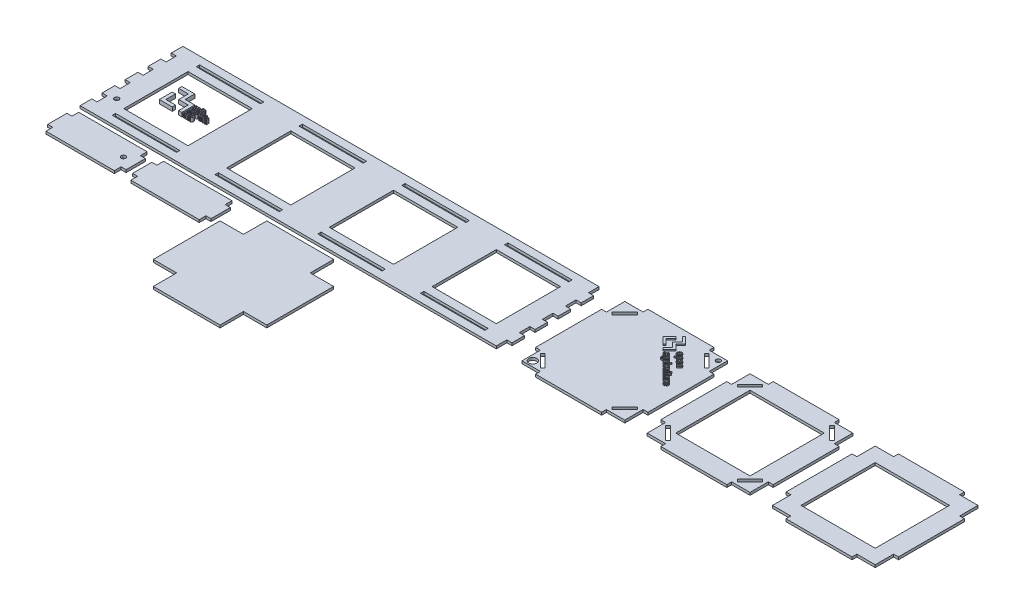
SolidWorks part; units mm, degrees
ref_plane "Front" through (0, 0, 0) normal (0, 0, 1) x (1, 0, 0)
ref_plane "Top" through (0, 0, 0) normal (0, 1, 0) x (1, 0, 0)
ref_plane "Right" through (0, 0, 0) normal (1, 0, 0) x (0, 0, -1)
sketch "Sketch1" plane through (0, 0, 0) normal (0, 1, 0) x (1, 0, 0)
  line L0 (0, 0) -> (152.4, 0) construction
  line L2 (-50.8, 50.8) -> (-50.8, -50.8) construction
  line L4 (50.8, 50.8) -> (50.8, -50.8) construction
  line L5 (-50.8, 50.8) -> (50.8, -50.8) construction
  line L6 (-50.8, -50.8) -> (50.8, 50.8) construction
  line L11 (50.8, 50.8) -> (152.4, 50.8)
  line L12 (50.8, 50.8) -> (50.8, -50.8) construction
  line L13 (50.8, -50.8) -> (152.4, -50.8)
  line L14 (152.4, 50.8) -> (152.4, -50.8) construction
  line L19 (-50.8, -50.8) -> (-152.4, -50.8)
  line L20 (-50.8, -50.8) -> (-50.8, 50.8) construction
  line L21 (-50.8, 50.8) -> (-152.4, 50.8)
  line L28 (50.8, -50.8) -> (-50.8, -50.8)
  line L34 (50.8, 50.8) -> (-50.8, 50.8)
  line L35 (-152.4, 50.8) -> (-152.4, -50.8) construction
  line L43 (-152.4, 50.8) -> (-254, 50.8)
  line L44 (-254, 50.8) -> (-254, -50.8) construction
  line L45 (-254, -50.8) -> (-152.4, -50.8)
  line L46 (152.4, 50.8) -> (152.4, 40.3352)
  line L47 (152.4, 40.3352) -> (157.48, 40.3352)
  line L48 (157.48, 40.3352) -> (157.48, 28.0162)
  line L49 (157.48, 28.0162) -> (152.4, 28.0162)
  line L50 (152.4, 28.0162) -> (152.4, 17.5514)
  line L51 (152.4, 17.5514) -> (157.48, 17.5514)
  line L63 (157.48, 17.5514) -> (157.48, 5.2324)
  line L64 (157.48, 5.2324) -> (152.4, 5.2324)
  line L65 (152.4, 5.2324) -> (152.4, -5.2324)
  line L66 (152.4, -5.2324) -> (157.48, -5.2324)
  line L67 (157.48, -5.2324) -> (157.48, -17.5514)
  line L68 (157.48, -17.5514) -> (152.4, -17.5514)
  line L69 (152.4, -17.5514) -> (152.4, -28.0162)
  line L70 (152.4, -28.0162) -> (157.48, -28.0162)
  line L71 (157.48, -28.0162) -> (157.48, -40.3352)
  line L72 (157.48, -40.3352) -> (152.4, -40.3352)
  line L73 (152.4, -40.3352) -> (152.4, -50.8)
  line L74 (-254, 50.8) -> (-259.08, 50.8)
  line L76 (-259.08, 39.2557) -> (-254, 39.2557)
  line L78 (-254, 29.0957) -> (-259.08, 29.0957)
  line L80 (-259.08, 16.4719) -> (-254, 16.4719)
  line L82 (-254, 6.3119) -> (-259.08, 6.3119)
  line L84 (-259.08, -6.3119) -> (-254, -6.3119)
  line L86 (-254, -16.4719) -> (-259.08, -16.4719)
  line L88 (-259.08, -29.0957) -> (-254, -29.0957)
  line L90 (-254, -39.2557) -> (-259.08, -39.2557)
  line L92 (-259.08, -50.8) -> (-254, -50.8)
  line L93 (157.48, 11.3919) -> (-254, 11.3919) construction
  line L94 (-254, 34.1757) -> (157.48, 34.1757) construction
  line L95 (-259.08, 50.8) -> (-259.08, 39.2557)
  line L96 (-259.08, 29.0957) -> (-259.08, 16.4719)
  line L97 (-254, 39.2557) -> (-254, 29.0957)
  line L98 (-254, 16.4719) -> (-254, 6.3119)
  line L99 (-254, -6.3119) -> (-254, -16.4719)
  line L100 (-254, -29.0957) -> (-254, -39.2557)
  line L101 (-254, -34.1757) -> (157.48, -34.1757) construction
  line L102 (-254, -11.3919) -> (157.48, -11.3919) construction
  line L103 (-259.08, 6.3119) -> (-259.08, -6.3119)
  line L104 (-259.08, -16.4719) -> (-259.08, -29.0957)
  line L105 (-259.08, -39.2557) -> (-259.08, -50.8)
  point P0 (0, 0)
  dimension "D1" = 101.6
  dimension "D2" = 101.6
  dimension "D3" = 5.08
  dimension "D4" = 12.319
  dimension "D5" = 10.16
extrude "Boss-Extrude1" add sketch "Sketch1" along normal blind 2.54
sketch "Sketch4" plane through (0, 2.54, 0) normal (0, 1, 0) x (1, 0, 0)
  line L0 (-152.4, 50.8) -> (-152.4, -50.8) construction
  line L1 (-152.4, 50.8) -> (-152.4, -50.8)
  line L2 (-50.8, 50.8) -> (-50.8, -50.8) construction
  line L3 (-50.8, 50.8) -> (-50.8, -50.8)
  line L4 (50.8, 50.8) -> (50.8, -50.8) construction
  line L5 (50.8, 50.8) -> (50.8, -50.8)
sketch "Sketch5" plane through (0, 2.54, 0) normal (0, 1, 0) x (1, 0, 0)
  line L0 (-254, -6.3119) -> (-254, 6.3119) construction
  line L1 (-152.4, 0) -> (-254, 0) construction
  line L2 (-152.4, 50.8) -> (-152.4, -50.8) construction
  line L3 (-152.4, 0) -> (-50.8, 0) construction
  line L4 (-50.8, 50.8) -> (-50.8, -50.8) construction
  line L5 (-50.8, 0) -> (50.8, 0) construction
  line L6 (50.8, 50.8) -> (50.8, -50.8) construction
  line L7 (50.8, 0) -> (152.4, 0) construction
  line L8 (152.4, -5.2324) -> (152.4, 5.2324) construction
  line L9 (-203.2, 0) -> (-203.2, -50.8) construction
  line L10 (-259.08, -50.8) -> (152.4, -50.8) construction
  line L11 (-101.6, 0) -> (-101.6, -50.8) construction
  line L12 (0, 0) -> (0, -50.8) construction
  line L13 (101.6, 0) -> (101.6, -50.8) construction
  line L14 (-171.45, -43.18) -> (-171.45, -50.8) construction
  line L15 (-234.95, -39.878) -> (-171.45, -39.878)
  line L16 (-234.95, -39.878) -> (-234.95, -43.18)
  line L17 (-234.95, -43.18) -> (-171.45, -43.18)
  line L18 (-171.45, -39.878) -> (-171.45, -43.18)
  line L19 (-234.95, -39.878) -> (-171.45, -43.18) construction
  line L20 (-234.95, -43.18) -> (-171.45, -39.878) construction
  line L21 (-133.35, -39.878) -> (-69.85, -39.878)
  line L22 (-133.35, -39.878) -> (-133.35, -43.18)
  line L23 (-133.35, -43.18) -> (-69.85, -43.18)
  line L24 (-69.85, -39.878) -> (-69.85, -43.18)
  line L25 (-133.35, -39.878) -> (-69.85, -43.18) construction
  line L26 (-133.35, -43.18) -> (-69.85, -39.878) construction
  line L27 (-31.75, -43.18) -> (31.75, -43.18)
  line L28 (-31.75, -43.18) -> (-31.75, -39.878)
  line L29 (-31.75, -39.878) -> (31.75, -39.878)
  line L30 (31.75, -43.18) -> (31.75, -39.878)
  line L31 (-31.75, -43.18) -> (31.75, -39.878) construction
  line L32 (-31.75, -39.878) -> (31.75, -43.18) construction
  line L33 (69.85, -43.18) -> (133.35, -43.18)
  line L34 (69.85, -43.18) -> (69.85, -39.878)
  line L35 (69.85, -39.878) -> (133.35, -39.878)
  line L36 (133.35, -43.18) -> (133.35, -39.878)
  line L37 (69.85, -43.18) -> (133.35, -39.878) construction
  line L38 (69.85, -39.878) -> (133.35, -43.18) construction
  line L39 (69.85, 39.878) -> (133.35, 43.18) construction
  line L40 (69.85, 43.18) -> (133.35, 39.878) construction
  line L41 (-31.75, 39.878) -> (31.75, 43.18) construction
  line L42 (-31.75, 43.18) -> (31.75, 39.878) construction
  line L43 (-133.35, 43.18) -> (-69.85, 39.878) construction
  line L44 (-133.35, 39.878) -> (-69.85, 43.18) construction
  line L45 (-234.95, 43.18) -> (-171.45, 39.878) construction
  line L46 (-234.95, 39.878) -> (-171.45, 43.18) construction
  line L47 (-171.45, 43.18) -> (-171.45, 50.8) construction
  line L48 (133.35, 43.18) -> (133.35, 39.878)
  line L49 (69.85, 39.878) -> (133.35, 39.878)
  line L50 (69.85, 43.18) -> (69.85, 39.878)
  line L51 (69.85, 43.18) -> (133.35, 43.18)
  line L52 (31.75, 43.18) -> (31.75, 39.878)
  line L53 (-31.75, 39.878) -> (31.75, 39.878)
  line L54 (-31.75, 43.18) -> (-31.75, 39.878)
  line L55 (-31.75, 43.18) -> (31.75, 43.18)
  line L56 (-69.85, 39.878) -> (-69.85, 43.18)
  line L57 (-133.35, 43.18) -> (-69.85, 43.18)
  line L58 (-133.35, 39.878) -> (-133.35, 43.18)
  line L59 (-133.35, 39.878) -> (-69.85, 39.878)
  line L60 (-171.45, 39.878) -> (-171.45, 43.18)
  line L61 (-234.95, 43.18) -> (-171.45, 43.18)
  line L62 (-234.95, 39.878) -> (-234.95, 43.18)
  line L63 (-234.95, 39.878) -> (-171.45, 39.878)
  line L65 (-234.95, 31.75) -> (-171.45, 31.75)
  line L66 (-234.95, 31.75) -> (-234.95, -31.75)
  line L67 (-234.95, -31.75) -> (-171.45, -31.75)
  line L68 (-171.45, 31.75) -> (-171.45, -31.75)
  line L69 (-234.95, 31.75) -> (-171.45, -31.75) construction
  line L70 (-234.95, -31.75) -> (-171.45, 31.75) construction
  line L71 (-133.35, 31.75) -> (-69.85, 31.75)
  line L72 (-133.35, 31.75) -> (-133.35, -31.75)
  line L73 (-133.35, -31.75) -> (-69.85, -31.75)
  line L74 (-69.85, 31.75) -> (-69.85, -31.75)
  line L75 (-133.35, 31.75) -> (-69.85, -31.75) construction
  line L76 (-133.35, -31.75) -> (-69.85, 31.75) construction
  line L77 (-31.75, 31.75) -> (31.75, 31.75)
  line L78 (-31.75, 31.75) -> (-31.75, -31.75)
  line L79 (-31.75, -31.75) -> (31.75, -31.75)
  line L80 (31.75, 31.75) -> (31.75, -31.75)
  line L81 (-31.75, 31.75) -> (31.75, -31.75) construction
  line L82 (-31.75, -31.75) -> (31.75, 31.75) construction
  line L83 (69.85, 31.75) -> (133.35, 31.75)
  line L84 (69.85, 31.75) -> (69.85, -31.75)
  line L85 (69.85, -31.75) -> (133.35, -31.75)
  line L86 (133.35, 31.75) -> (133.35, -31.75)
  line L87 (69.85, 31.75) -> (133.35, -31.75) construction
  line L88 (69.85, -31.75) -> (133.35, 31.75) construction
  circle A0 centre (-246.95, -26.75) radius 2.2225
  point P27 (-203.2, -41.529)
  point P32 (-101.6, -41.529)
  point P37 (0, -41.529)
  point P42 (101.6, -41.529)
  point P66 (101.6, 41.529)
  point P67 (0, 41.529)
  point P68 (-101.6, 41.529)
  point P69 (-203.2, 41.529)
  dimension "D5" = 4.445
  dimension "D7" = 5
  dimension "D1" = 7.62
  dimension "D2" = 3.302
  dimension "D3" = 63.5
  dimension "D4" = 63.5
  dimension "D6" = 12
extrude "Cut-Extrude2" cut sketch "Sketch5" against normal through all
sketch "Sketch6" plane through (0, 0, 0) normal (0, 1, 0) x (1, 0, 0)
  line L0 (0, 0) -> (228.6, 0) construction
  line L1 (228.6, 0) -> (228.6, 53.1812) construction
  line L2 (177.8, 50.8) -> (279.4, 50.8) construction
  line L3 (177.8, 50.8) -> (177.8, -50.8) construction
  line L4 (177.8, -50.8) -> (279.4, -50.8) construction
  line L5 (279.4, 50.8) -> (279.4, -50.8) construction
  line L6 (177.8, 50.8) -> (279.4, -50.8) construction
  line L7 (177.8, -50.8) -> (279.4, 50.8) construction
  line L8 (228.6, 0) -> (281.7812, 0) construction
  line L9 (228.6, 0) -> (228.6, -53.1812) construction
  line L10 (177.8, 32.639) -> (177.8, 50.8)
  line L11 (195.961, 55.5625) -> (261.239, 55.5625)
  line L12 (195.961, 55.5625) -> (195.961, 50.8)
  line L13 (195.961, 50.8) -> (261.239, 50.8) construction
  line L14 (261.239, 55.5625) -> (261.239, 50.8)
  line L15 (195.961, 55.5625) -> (261.239, 50.8) construction
  line L16 (195.961, 50.8) -> (261.239, 55.5625) construction
  line L17 (284.1625, -32.639) -> (279.4, -32.639)
  line L18 (284.1625, -32.639) -> (284.1625, 32.639)
  line L19 (284.1625, 32.639) -> (279.4, 32.639)
  line L20 (279.4, -32.639) -> (279.4, 32.639) construction
  line L21 (284.1625, -32.639) -> (279.4, 32.639) construction
  line L22 (284.1625, 32.639) -> (279.4, -32.639) construction
  line L23 (195.961, -55.5625) -> (261.239, -55.5625)
  line L24 (195.961, -55.5625) -> (195.961, -50.8)
  line L25 (195.961, -50.8) -> (261.239, -50.8) construction
  line L26 (261.239, -55.5625) -> (261.239, -50.8)
  line L27 (195.961, -55.5625) -> (261.239, -50.8) construction
  line L28 (195.961, -50.8) -> (261.239, -55.5625) construction
  line L29 (173.0375, 32.639) -> (177.8, 32.639)
  line L30 (173.0375, 32.639) -> (173.0375, -32.639)
  line L31 (173.0375, -32.639) -> (177.8, -32.639)
  line L32 (177.8, 32.639) -> (177.8, -32.639) construction
  line L33 (173.0375, 32.639) -> (177.8, -32.639) construction
  line L34 (173.0375, -32.639) -> (177.8, 32.639) construction
  line L35 (177.8, 50.8) -> (195.961, 50.8)
  line L36 (261.239, 50.8) -> (279.4, 50.8)
  line L37 (279.4, 50.8) -> (279.4, 32.639)
  line L38 (279.4, -32.639) -> (279.4, -50.8)
  line L39 (279.4, -50.8) -> (261.239, -50.8)
  line L40 (195.961, -50.8) -> (177.8, -50.8)
  line L41 (177.8, -50.8) -> (177.8, -32.639)
  line L42 (296.8625, 32.639) -> (296.8625, -32.639)
  line L43 (296.8625, 32.639) -> (301.625, 32.639)
  line L44 (301.625, 32.639) -> (301.625, 50.8)
  line L45 (301.625, 50.8) -> (319.786, 50.8)
  line L46 (319.786, 55.5625) -> (319.786, 50.8)
  line L47 (319.786, 55.5625) -> (385.064, 55.5625)
  line L48 (385.064, 55.5625) -> (385.064, 50.8)
  line L49 (385.064, 50.8) -> (403.225, 50.8)
  line L50 (403.225, 50.8) -> (403.225, 32.639)
  line L51 (407.9875, 32.639) -> (403.225, 32.639)
  line L52 (407.9875, -32.639) -> (407.9875, 32.639)
  line L53 (407.9875, -32.639) -> (403.225, -32.639)
  line L54 (403.225, -32.639) -> (403.225, -50.8)
  line L55 (403.225, -50.8) -> (385.064, -50.8)
  line L56 (385.064, -55.5625) -> (385.064, -50.8)
  line L57 (319.786, -55.5625) -> (385.064, -55.5625)
  line L58 (319.786, -55.5625) -> (319.786, -50.8)
  line L59 (319.786, -50.8) -> (301.625, -50.8)
  line L60 (301.625, -50.8) -> (301.625, -32.639)
  line L61 (296.8625, -32.639) -> (301.625, -32.639)
  line L62 (301.625, 50.8) -> (403.225, -50.8) construction
  line L63 (420.6875, 32.639) -> (420.6875, -32.639)
  line L64 (420.6875, 32.639) -> (425.45, 32.639)
  line L65 (425.45, 32.639) -> (425.45, 50.8)
  line L66 (425.45, 50.8) -> (443.611, 50.8)
  line L67 (443.611, 55.5625) -> (443.611, 50.8)
  line L68 (443.611, 55.5625) -> (508.889, 55.5625)
  line L69 (508.889, 55.5625) -> (508.889, 50.8)
  line L70 (508.889, 50.8) -> (527.05, 50.8)
  line L71 (527.05, 50.8) -> (527.05, 32.639)
  line L72 (531.8125, 32.639) -> (527.05, 32.639)
  line L73 (531.8125, -32.639) -> (531.8125, 32.639)
  line L74 (531.8125, -32.639) -> (527.05, -32.639)
  line L75 (527.05, -32.639) -> (527.05, -50.8)
  line L76 (527.05, -50.8) -> (508.889, -50.8)
  line L77 (508.889, -55.5625) -> (508.889, -50.8)
  line L78 (443.611, -55.5625) -> (508.889, -55.5625)
  line L79 (443.611, -55.5625) -> (443.611, -50.8)
  line L80 (443.611, -50.8) -> (425.45, -50.8)
  line L81 (425.45, -50.8) -> (425.45, -32.639)
  line L82 (420.6875, -32.639) -> (425.45, -32.639)
  line L83 (425.45, 50.8) -> (527.05, -50.8) construction
  line L84 (315.722, 36.703) -> (389.128, 36.703)
  line L85 (315.722, 36.703) -> (315.722, -36.703)
  line L86 (315.722, -36.703) -> (389.128, -36.703)
  line L87 (389.128, 36.703) -> (389.128, -36.703)
  line L88 (315.722, 36.703) -> (389.128, -36.703) construction
  line L89 (315.722, -36.703) -> (389.128, 36.703) construction
  line L91 (512.953, 36.703) -> (439.547, 36.703)
  line L92 (512.953, 36.703) -> (512.953, -36.703)
  line L93 (512.953, -36.703) -> (439.547, -36.703)
  line L94 (439.547, 36.703) -> (439.547, -36.703)
  line L95 (512.953, 36.703) -> (439.547, -36.703) construction
  line L96 (512.953, -36.703) -> (439.547, 36.703) construction
  point P22 (175.4187, 0)
  point P67 (352.425, 0)
  point P72 (476.25, 0)
  dimension "D1" = 101.6
  dimension "D2" = 101.6
  dimension "D3" = 4.7625
  dimension "D4" = 65.278
  dimension "D5" = 228.6
  dimension "D7" = 12.7
  dimension "D8" = 73.406
  dimension "D6" = 3
extrude "Boss-Extrude2" add sketch "Sketch6" along normal blind 2.54 separate body
sketch "Sketch7" plane through (0, 0, 0) normal (0, 1, 0) x (1, 0, 0)
  line L0 (-234.95, 39.878) -> (-234.95, -27.686) construction
  line L1 (-254.08, -57.15) -> (-186.516, -57.15)
  line L2 (-254.08, -57.15) -> (-254.08, -63.8175)
  line L3 (-254.08, -89.535) -> (-186.516, -89.535)
  line L4 (-186.516, -57.15) -> (-186.516, -63.8175)
  line L5 (-254.08, -57.15) -> (-186.516, -89.535) construction
  line L6 (-254.08, -89.535) -> (-186.516, -57.15) construction
  line L7 (-234.95, 31.75) -> (-234.95, -31.75) construction
  line L8 (-234.95, -27.686) -> (-234.95, -31.75) construction
  line L9 (177.8, -32.639) -> (177.8, -50.8) construction
  line L10 (177.8, -50.8) -> (195.961, -50.8) construction
  line L12 (-254.08, -63.8175) -> (-259.08, -63.8175)
  line L13 (182.9292, -33.0985) -> (195.5015, -45.6708) construction
  line L14 (182.9292, -33.0985) -> (180.5943, -35.4333) construction
  line L15 (180.5943, -35.4333) -> (193.1667, -48.0057) construction
  line L16 (195.5015, -45.6708) -> (193.1667, -48.0057) construction
  line L17 (182.9292, -33.0985) -> (193.1667, -48.0057) construction
  line L18 (180.5943, -35.4333) -> (195.5015, -45.6708) construction
  line L19 (-259.08, -63.8175) -> (-259.08, -82.8675)
  line L20 (-259.08, -82.8675) -> (-254.08, -82.8675)
  line L21 (177.8, -32.639) -> (195.961, -50.8) construction
  line L22 (188.0479, -40.5521) -> (186.8805, -41.7195) construction
  line L23 (-254.08, -82.8675) -> (-254.08, -89.535)
  line L24 (-186.516, -63.8175) -> (-181.516, -63.8175)
  line L25 (-181.516, -63.8175) -> (-181.516, -82.8675)
  line L26 (-181.516, -82.8675) -> (-186.516, -82.8675)
  line L27 (-186.516, -82.8675) -> (-186.516, -89.535)
  line L28 (-259.08, -50.8) -> (152.4, -50.8) construction
  line L29 (-259.08, -39.2557) -> (-259.08, -50.8) construction
  line L30 (-170.166, -57.15) -> (-102.602, -57.15)
  line L31 (-170.166, -57.15) -> (-170.166, -63.8175)
  line L32 (-170.166, -89.535) -> (-102.602, -89.535)
  line L33 (-102.602, -57.15) -> (-102.602, -63.8175)
  line L34 (-170.166, -63.8175) -> (-175.166, -63.8175)
  line L35 (-175.166, -63.8175) -> (-175.166, -82.8675)
  line L36 (-175.166, -82.8675) -> (-170.166, -82.8675)
  line L37 (-170.166, -82.8675) -> (-170.166, -89.535)
  line L38 (-102.602, -63.8175) -> (-97.602, -63.8175)
  line L39 (-97.602, -63.8175) -> (-97.602, -82.8675)
  line L40 (-97.602, -82.8675) -> (-102.602, -82.8675)
  line L41 (-102.602, -82.8675) -> (-102.602, -89.535)
  line L42 (-170.166, -57.15) -> (-102.602, -89.535) construction
  line L43 (-170.166, -89.535) -> (-102.602, -57.15) construction
  point P0 (-220.298, -73.3425)
  point P14 (188.0479, -40.5521)
  point P38 (-136.384, -73.3425)
  dimension "D1" = 32.385
  dimension "D2" = 4.064
  dimension "D3" = 3.302
  dimension "D4" = 19.05
  dimension "D5" = 17.78
  dimension "D6" = 5
  dimension "D7" = 6.35
  dimension "D9" = 6.35
  dimension "D8" = 2
extrude "Boss-Extrude3" add sketch "Sketch7" along normal blind 2.54 separate body
sketch "Sketch8" plane through (0, 2.54, 0) normal (0, 1, 0) x (1, 0, 0)
  line L0 (180.5943, -35.4333) -> (193.1667, -48.0057) construction
  line L1 (195.5015, -45.6708) -> (193.1667, -48.0057) construction
  line L2 (182.9292, -33.0985) -> (195.5015, -45.6708) construction
  line L3 (182.9292, -33.0985) -> (180.5943, -35.4333) construction
  line L4 (180.5943, -35.4333) -> (193.1667, -48.0057)
  line L5 (195.5015, -45.6708) -> (193.1667, -48.0057)
  line L6 (182.9292, -33.0985) -> (195.5015, -45.6708)
  line L7 (182.9292, -33.0985) -> (180.5943, -35.4333)
  line L8 (177.8, 50.8) -> (279.4, -50.8) construction
  line L9 (195.5015, 45.6708) -> (182.9292, 33.0985)
  line L10 (195.5015, 45.6708) -> (193.1667, 48.0057)
  line L11 (193.1667, 48.0057) -> (180.5943, 35.4333)
  line L12 (182.9292, 33.0985) -> (180.5943, 35.4333)
  line L13 (274.2708, 33.0985) -> (261.6985, 45.6708)
  line L14 (274.2708, 33.0985) -> (276.6057, 35.4333)
  line L15 (276.6057, 35.4333) -> (264.0333, 48.0057)
  line L16 (261.6985, 45.6708) -> (264.0333, 48.0057)
  line L17 (261.6985, -45.6708) -> (274.2708, -33.0985)
  line L18 (261.6985, -45.6708) -> (264.0333, -48.0057)
  line L19 (264.0333, -48.0057) -> (276.6057, -35.4333)
  line L20 (274.2708, -33.0985) -> (276.6057, -35.4333)
  line L21 (301.625, -32.639) -> (319.786, -50.8) construction
  line L22 (304.4193, -35.4333) -> (306.7542, -33.0985)
  line L23 (306.7542, -33.0985) -> (319.3265, -45.6708)
  line L24 (319.3265, -45.6708) -> (316.9917, -48.0057)
  line L25 (310.7055, -41.7195) -> (313.0404, -39.3846) construction
  line L26 (304.4193, -35.4333) -> (316.9917, -48.0057)
  line L27 (301.625, 50.8) -> (403.225, -50.8) construction
  line L28 (306.7542, 33.0985) -> (304.4193, 35.4333)
  line L29 (316.9917, 48.0057) -> (304.4193, 35.4333)
  line L30 (316.9917, 48.0057) -> (319.3265, 45.6708)
  line L31 (319.3265, 45.6708) -> (306.7542, 33.0985)
  line L32 (385.5235, 45.6708) -> (387.8583, 48.0057)
  line L33 (400.4307, 35.4333) -> (387.8583, 48.0057)
  line L34 (400.4307, 35.4333) -> (398.0958, 33.0985)
  line L35 (398.0958, 33.0985) -> (385.5235, 45.6708)
  line L36 (398.0958, -33.0985) -> (400.4307, -35.4333)
  line L37 (387.8583, -48.0057) -> (400.4307, -35.4333)
  line L38 (387.8583, -48.0057) -> (385.5235, -45.6708)
  line L39 (385.5235, -45.6708) -> (398.0958, -33.0985)
  circle A0 centre (228.6, 0) radius 20.7898 construction
  circle A1 centre (228.6, 0) radius 20.7898 construction
  circle A2 centre (228.6, 0) radius 20.7898 construction
  circle A3 centre (228.6, 0) radius 20.7898 construction
  circle A4 centre (352.425, 0) radius 51.9059 construction
  point P28 (228.6, 0)
  point P58 (352.425, 0)
  dimension "D1" = 4
  dimension "D2" = 4
extrude "Cut-Extrude3" cut sketch "Sketch8" against normal through all
sketch "Sketch10" plane through (0, 2.54, 0) normal (0, 1, 0) x (1, 0, 0)
  line L0 (-171.45, 31.75) -> (-234.95, 31.75) construction
  line L1 (-69.85, 31.75) -> (-133.35, 31.75) construction
  line L2 (31.75, 31.75) -> (-31.75, 31.75) construction
  line L3 (133.35, 31.75) -> (69.85, 31.75) construction
  line L4 (-196.85, 31.75) -> (-209.55, 31.75)
  line L5 (-95.25, 31.75) -> (-107.95, 31.75)
  line L6 (6.35, 31.75) -> (-6.35, 31.75)
  line L7 (107.95, 31.75) -> (95.25, 31.75)
  line L8 (-234.95, -27.686) -> (-171.45, -27.686)
  line L9 (-203.2, -27.686) -> (-203.2, -31.75) construction
  line L14 (-234.95, 31.75) -> (-234.95, -31.75) construction
  line L15 (-171.45, -31.75) -> (-171.45, 31.75) construction
  line L16 (-234.95, -31.75) -> (-171.45, -31.75) construction
  line L17 (-133.35, -27.686) -> (-69.85, -27.686)
  line L18 (-133.35, 31.75) -> (-133.35, -31.75) construction
  line L19 (-69.85, -31.75) -> (-69.85, 31.75) construction
  line L20 (-31.75, -27.686) -> (31.75, -27.686)
  line L21 (-31.75, 31.75) -> (-31.75, -31.75) construction
  line L22 (31.75, -31.75) -> (31.75, 31.75) construction
  line L23 (69.85, -27.686) -> (133.35, -27.686)
  line L24 (69.85, 31.75) -> (69.85, -31.75) construction
  line L25 (133.35, -31.75) -> (133.35, 31.75) construction
  line L27 (-234.95, 31.75) -> (-234.95, -27.686) construction
  arc A0 (-209.55, 31.75) -> (-196.85, 31.75) centre (-203.2, 31.75) ccw
  arc A1 (-107.95, 31.75) -> (-95.25, 31.75) centre (-101.6, 31.75) ccw
  arc A2 (-6.35, 31.75) -> (6.35, 31.75) centre (0, 31.75) ccw
  arc A3 (95.25, 31.75) -> (107.95, 31.75) centre (101.6, 31.75) ccw
  dimension "D1" = 12.7
  dimension "D2" = 4.064
sketch "Sketch11" plane through (0, 0, 0) normal (0, 1, 0) x (1, 0, 0)
  line L0 (-133.35, -31.75) -> (-133.35, -39.878) construction
  line L5 (-68.138, -80.264) -> (-2.098, -80.264) construction
  line L6 (-68.138, -80.264) -> (-68.138, -146.304) construction
  line L7 (-68.138, -146.304) -> (-2.098, -146.304) construction
  line L8 (-2.098, -80.264) -> (-2.098, -146.304) construction
  line L9 (-68.138, -80.264) -> (-2.098, -146.304) construction
  line L10 (-68.138, -146.304) -> (-2.098, -80.264) construction
  line L11 (-68.138, -80.264) -> (-91.252, -80.264)
  line L12 (-91.252, -80.264) -> (-91.252, -146.304)
  line L13 (-91.252, -146.304) -> (-68.138, -146.304)
  line L14 (-68.138, -80.264) -> (-68.138, -57.15)
  line L15 (-68.138, -57.15) -> (-2.098, -57.15)
  line L16 (-2.098, -57.15) -> (-2.098, -80.264)
  line L17 (-2.098, -80.264) -> (21.016, -80.264)
  line L18 (21.016, -80.264) -> (21.016, -146.304)
  line L19 (21.016, -146.304) -> (-2.098, -146.304)
  line L20 (-2.098, -146.304) -> (-2.098, -169.418)
  line L21 (-2.098, -169.418) -> (-68.138, -169.418)
  line L22 (-68.138, -169.418) -> (-68.138, -146.304)
  line L23 (-259.08, -50.8) -> (152.4, -50.8) construction
  line L24 (-97.602, -82.8675) -> (-97.602, -63.8175) construction
  line L27 (133.35, -27.686) -> (133.35, -50.8) construction
  point P0 (-35.118, -113.284)
  dimension "D1" = 66.04
  dimension "D4" = 6.35
  dimension "D5" = 6.35
extrude "Boss-Extrude5" add sketch "Sketch11" along normal blind 2.54 separate body
sketch "Sketch12" plane through (0, 2.54, 0) normal (0, 1, 0) x (1, 0, 0)
  line L0 (-68.138, -80.264) -> (-2.098, -80.264)
  line L1 (-2.098, -80.264) -> (-2.098, -146.304)
  line L2 (-2.098, -146.304) -> (-68.138, -146.304)
  line L3 (-68.138, -80.264) -> (-68.138, -146.304)
sketch "Sketch13" plane through (0, 0, 0) normal (0, 1, 0) x (1, 0, 0)
  line L16 (-223.9443, 14.6616) -> (-211.1797, 14.6616)
  line L17 (-211.1797, 14.6616) -> (-211.1797, 5.1786)
  line L18 (-211.1797, 5.1786) -> (-201.7193, 5.1786)
  line L19 (239.1402, 49.5353) -> (245.5874, 43.0882)
  line L20 (245.5874, 43.0882) -> (240.7977, 38.2986)
  line L21 (240.7977, 38.2986) -> (245.5759, 33.5204)
  line L22 (245.5759, 33.5204) -> (239.1174, 27.0618)
  line L24 (237.5056, 28.6736) -> (242.3295, 33.4975)
  line L25 (242.3295, 33.4975) -> (237.5627, 38.2643)
  line L26 (237.5627, 38.2643) -> (242.3752, 43.0768)
  line L27 (242.3752, 43.0768) -> (237.5284, 47.9235)
  line L28 (237.5284, 47.9235) -> (239.1402, 49.5353)
  line L29 (234.3506, 44.7457) -> (235.9738, 43.1225)
  line L30 (235.9738, 43.1225) -> (231.1385, 38.2871)
  line L31 (231.1385, 38.2871) -> (235.9624, 33.4632)
  line L32 (235.9624, 33.4632) -> (234.3392, 31.84)
  line L33 (234.3392, 31.84) -> (227.892, 38.2871)
  line L34 (227.892, 38.2871) -> (234.3506, 44.7457)
  line L36 (239.5771, 26.9975) -> (266.5291, 0.0455) construction
  line L37 (247.4273, 32.1428) -> (285.1667, -5.5965) construction
  line L38 (237.5056, 28.6736) -> (239.1174, 27.0618)
  line L41 (-201.7193, 5.1786) -> (-201.7193, -7.6086)
  line L43 (-204.9105, -7.6086) -> (-204.9105, 1.9422)
  line L44 (-204.9105, 1.9422) -> (-214.3482, 1.9422)
  line L45 (-214.3482, 1.9422) -> (-214.3482, 11.4705)
  line L46 (-214.3482, 11.4705) -> (-223.9443, 11.4705)
  line L47 (-223.9443, 11.4705) -> (-223.9443, 14.6616)
  line L48 (-223.9443, 5.1786) -> (-220.7305, 5.1786)
  line L49 (-220.7305, 5.1786) -> (-220.7305, -4.3949)
  line L50 (-220.7305, -4.3949) -> (-211.1797, -4.3949)
  line L51 (-211.1797, -4.3949) -> (-211.1797, -7.6086)
  line L52 (-211.1797, -7.6086) -> (-223.9443, -7.6086)
  line L53 (-223.9443, -7.6086) -> (-223.9443, 5.1786)
  line L54 (-200.854, -7.608) -> (-149.188, -7.608) construction
  line L55 (-234.95, 31.75) -> (-171.45, -27.686) construction
  line L56 (-204.9105, -7.6086) -> (-201.7193, -7.6086)
  line L57 (-200.854, -7.608) -> (-200.854, 5.1786) construction
  line L58 (-200.854, 5.1786) -> (-201.7193, 5.1786) construction
  line L59 (-200.854, 1.9422) -> (-182.9615, 1.9422) construction
  line L60 (-200.854, -2.3557) -> (-181.4784, -2.3557) construction
  line L61 (-234.95, 31.75) -> (-234.95, -31.75) construction
  line L62 (-196.85, 6.35) -> (-209.55, 6.35) construction
  line L63 (-196.85, 6.35) -> (-196.85, -2.286) construction
  line L64 (-196.85, -2.286) -> (-209.55, -2.286) construction
  line L65 (-209.55, 6.35) -> (-209.55, -2.286) construction
  line L66 (-196.85, 6.35) -> (-209.55, -2.286) construction
  line L67 (-196.85, -2.286) -> (-209.55, 6.35) construction
  line L68 (-171.45, 31.75) -> (-234.95, 31.75) construction
  line L69 (-234.95, -27.686) -> (-171.45, -27.686) construction
  line L70 (-171.45, -31.75) -> (-171.45, 31.75) construction
  text T0 "mit" font "Arial" height in points 18
  text T1 "media" font "Arial" height in points 18
  text T2 "lab" font "Arial" height in points 18
  text T3 "open" font "Arial" height in points 24
  text T4 " agriculture" font "Arial" height in points 24
  point P56 (-194.7375, 4.459)
  dimension "D1" = 25.4
  dimension "D4" = 25.4
  dimension "D5" = 25.4
  dimension "D6" = 25.4
sketch "Sketch14" plane through (0, 2.54, 0) normal (0, 1, 0) x (1, 0, 0)
  line L0 (-181.516, -73.3425) -> (-193.7385, -73.3425) construction
  line L1 (-181.516, -82.8675) -> (-181.516, -63.8175) construction
  circle A0 centre (-193.7385, -73.3425) radius 2.2225
  circle A1 centre (-246.95, -26.75) radius 2.2225 construction
  dimension "D1" = 10
extrude "Cut-Extrude4" cut sketch "Sketch14" against normal through all
extrude "Boss-Extrude7" add sketch "Sketch13" along normal blind 3.81 separate body
sketch "Sketch15" plane through (0, 2.54, 0) normal (0, 1, 0) x (1, 0, 0)
  line L0 (177.8, -50.8) -> (186.8805, -41.7195) construction
  line L1 (180.5943, -35.4333) -> (193.1667, -48.0057) construction
  line L2 (183.1192, -51.5768) -> (183.1192, -50.8) construction
  line L3 (177.8, -50.8) -> (195.961, -50.8) construction
  line L4 (186.8805, -41.7195) -> (187.4298, -41.1702) construction
  line L5 (177.8, 50.8) -> (279.4, -50.8) construction
  line L6 (279.4, 50.8) -> (270.3195, 41.7195) construction
  line L7 (276.6057, 35.4333) -> (264.0333, 48.0057) construction
  circle A0 centre (183.1192, -45.4808) radius 3.95
  circle A1 centre (183.1192, -45.4808) radius 6.096 construction
  circle A2 centre (274.8598, 46.2598) radius 2.2225
  circle A3 centre (-193.7385, -73.3425) radius 2.2225 construction
  dimension "D1" = 7.9
  dimension "D2" = 12.192
extrude "Cut-Extrude5" cut sketch "Sketch15" against normal through all
sketch "Sketch16" plane through (0, 2.54, 0) normal (0, 1, 0) x (1, 0, 0)
  line L0 (315.722, 36.703) -> (315.722, -36.703) construction
  line L1 (318.897, 4.953) -> (481.6251, 4.953) construction
  line L2 (318.897, 24.003) -> (356.997, 24.003)
  line L3 (318.897, 24.003) -> (318.897, -14.097)
  line L4 (318.897, -14.097) -> (356.997, -14.097)
  line L6 (318.897, 24.003) -> (356.997, -14.097) construction
  line L7 (318.897, -14.097) -> (356.997, 24.003) construction
  line L8 (481.6251, 4.953) -> (337.947, 4.953) construction
  line L9 (356.997, 24.003) -> (356.997, 7.3274)
  line L10 (361.4118, 10.5046) -> (361.3272, 10.6511)
  line L11 (337.947, 24.003) -> (337.947, -14.097) construction
  line L12 (350.647, 10.033) -> (341.249, 10.033)
  line L13 (350.647, -0.127) -> (341.249, -0.127)
  line L14 (337.947, 10.033) -> (337.947, -0.127) construction
  line L15 (361.061, 10.033) -> (337.947, 10.033) construction
  line L16 (361.061, -0.127) -> (337.947, -0.127) construction
  line L17 (353.8503, 9.1658) -> (358.5112, 6.4427)
  line L18 (361.061, 4.953) -> (360.3382, 4.953) construction
  line L19 (361.061, 4.953) -> (337.947, 4.953) construction
  line L20 (376.3171, 4.953) -> (360.3382, 4.953) construction
  line L21 (350.647, 10.033) -> (350.647, -0.127) construction
  line L22 (356.997, -9.6369) -> (356.997, -14.097)
  line L23 (389.128, 36.703) -> (315.722, 36.703) construction
  line L24 (337.947, 13.335) -> (337.947, 13.843) construction
  line L25 (337.947, -3.429) -> (337.947, -3.937) construction
  line L26 (337.947, 13.335) -> (337.947, -3.429)
  arc A1 (361.4512, 3.3336) -> (364.7388, 8.5069) centre (364.617, 4.953) ccw
  arc A3 (364.8818, 16.6501) -> (361.3272, 10.6511) centre (364.7913, 12.6511) ccw
  arc A4 (361.4118, 10.5046) -> (364.7388, 8.5069) centre (364.8759, 12.5046) ccw
  arc A5 (353.8503, 9.1658) -> (350.647, 10.033) centre (350.647, 3.683) ccw
  arc A6 (355.5616, -2.4559) -> (350.647, -0.127) centre (350.647, -6.477) ccw
  arc A7 (361.4512, 3.3336) -> (358.5112, 6.4427) centre (354.6672, -0.1367) ccw
  arc A8 (341.249, -0.127) -> (337.947, -3.429) centre (341.249, -3.429) ccw
  arc A9 (337.947, 13.335) -> (341.249, 10.033) centre (341.249, 13.335) ccw
  arc A10 (355.5616, -2.4559) -> (364.8818, 16.6501) centre (364.617, 4.953) ccw
  point P4 (337.947, 4.953)
  point P28 (371.8905, 14.7821)
  dimension "D7" = 4
  dimension "D8" = 6.35
  dimension "D9" = 6.35
  dimension "D10" = 7.62
  dimension "D12" = 7.112
  dimension "D17" = 3.302
  dimension "D1" = 38.1
  dimension "D2" = 38.1
  dimension "D3" = 12.7
  dimension "D4" = 5.08
  dimension "D6" = 30
  dimension "D11" = 26.67
  dimension "D13" = 3.175
  dimension "D14" = 12.7
  dimension "D15" = 3.81
  dimension "D16" = 3.81
  dimension "D5" = 5.08
sketch "Sketch17" plane through (0, 2.54, 0) normal (0, 1, 0) x (1, 0, 0)
  line L1 (228.6, 55.5625) -> (228.6, -55.5625) construction
  line L5 (318.897, 24.003) -> (356.997, 24.003) construction
  line L6 (318.897, 24.003) -> (356.997, 24.003)
  line L7 (356.997, 24.003) -> (356.997, 7.3274) construction
  line L8 (318.897, 24.003) -> (318.897, -14.097) construction
  line L9 (318.897, -14.097) -> (356.997, -14.097) construction
  line L12 (261.239, 55.5625) -> (195.961, 55.5625) construction
  line L13 (195.961, -55.5625) -> (261.239, -55.5625) construction
  line L14 (356.997, -9.6369) -> (356.997, -14.097) construction
  line L15 (356.997, 24.003) -> (356.997, 7.3274)
  line L16 (350.647, 10.033) -> (341.249, 10.033)
  line L17 (337.947, 13.335) -> (337.947, -3.429)
  line L18 (341.249, -0.127) -> (350.647, -0.127)
  line L19 (361.3272, 10.6511) -> (361.4118, 10.5046)
  line L20 (358.5112, 6.4427) -> (353.8503, 9.1658)
  line L21 (350.647, 10.033) -> (341.249, 10.033)
  line L23 (341.249, -0.127) -> (350.647, -0.127)
  line L24 (361.3272, 10.6511) -> (361.4118, 10.5046)
  line L25 (358.5112, 6.4427) -> (353.8503, 9.1658)
  line L26 (318.897, 24.003) -> (356.997, 24.003)
  line L27 (318.897, 24.003) -> (318.897, -14.097)
  line L28 (318.897, -14.097) -> (356.997, -14.097)
  line L29 (356.997, -3.9255) -> (356.997, -14.097)
  line L30 (228.6, 8.382) -> (228.6, -8.382) construction
  line L31 (201.93, 0) -> (255.27, 0) construction
  line L32 (208.0731, 1.5292) -> (212.7339, 4.2292)
  line L34 (225.298, -5.08) -> (215.9, -5.08)
  line L35 (215.9, 5.08) -> (225.298, 5.08)
  arc A9 (212.7339, 4.2292) -> (215.9, 5.08) centre (215.9, -1.2362) cw
  arc A10 (205.0999, -1.6114) -> (208.0731, 1.5292) centre (211.8927, -5.0644) cw
  arc A11 (205.0999, -1.6114) -> (202.1617, 3.5484) centre (201.93, 0) cw
  arc A14 (210.9854, -7.4089) -> (202.6925, 11.6752) centre (201.93, 0) cw
  arc A15 (210.9854, -7.4089) -> (215.9, -5.08) centre (215.9, -11.43) cw
  arc A16 (225.298, -5.08) -> (228.6, -8.382) centre (225.298, -8.382) cw
  arc A17 (228.6, 8.382) -> (225.298, 5.08) centre (225.298, 8.382) cw
  arc A18 (337.947, 13.335) -> (341.249, 10.033) centre (341.249, 13.335) ccw
  arc A19 (341.249, -0.127) -> (337.947, -3.429) centre (341.249, -3.429) ccw
  arc A20 (355.5616, -2.4559) -> (350.647, -0.127) centre (350.647, -6.477) ccw
  arc A21 (355.5616, -2.4559) -> (364.8818, 16.6501) centre (364.617, 4.953) ccw
  arc A22 (364.8818, 16.6501) -> (361.3272, 10.6511) centre (364.7913, 12.6511) ccw
  arc A23 (361.4118, 10.5046) -> (364.7388, 8.5069) centre (364.8759, 12.5046) ccw
  arc A24 (361.4512, 3.3336) -> (364.7388, 8.5069) centre (364.617, 4.953) ccw
  arc A25 (361.4512, 3.3336) -> (358.5112, 6.4427) centre (354.6672, -0.1367) ccw
  arc A26 (353.8503, 9.1658) -> (350.647, 10.033) centre (350.647, 3.683) ccw
  arc A27 (337.947, 13.335) -> (341.249, 10.033) centre (341.249, 13.335) ccw
  arc A28 (341.249, -0.127) -> (337.947, -3.429) centre (341.249, -3.429) ccw
  arc A29 (355.5616, -2.4559) -> (350.647, -0.127) centre (350.647, -6.477) ccw
  arc A30 (355.5616, -2.4559) -> (364.8818, 16.6501) centre (364.617, 4.953) ccw
  arc A31 (364.8818, 16.6501) -> (361.3272, 10.6511) centre (364.7913, 12.6511) ccw
  arc A32 (361.4118, 10.5046) -> (364.7388, 8.5069) centre (364.8759, 12.5046) ccw
  arc A33 (361.4512, 3.3336) -> (364.7388, 8.5069) centre (364.617, 4.953) ccw
  arc A34 (361.4512, 3.3336) -> (358.5112, 6.4427) centre (354.6672, -0.1367) ccw
  arc A35 (353.8503, 9.1658) -> (350.647, 10.033) centre (350.647, 3.683) ccw
  arc A36 (202.6925, 11.6752) -> (202.1617, 3.5484) centre (202.4271, 7.6118) cw
  point P32 (202.3814, 3.4269)
  point P33 (202.1538, 3.4269)
  point P38 (212.7701, 4.0858)
  point P43 (228.6, 0)
  point P64 (228.6, 0)
  dimension "D4" = 11.7001
  dimension "D5" = 10.16
  dimension "D6" = 3.302
  dimension "D2" = 26.67
  dimension "D3" = 3.556
  dimension "D8" = 0.4971
  dimension "D9" = 7.62
  dimension "D7" = 16.764
  dimension "D10" = 4.6609
  dimension "D11" = 12.7
  dimension "D12" = 30.084
  dimension "D1" = 0
